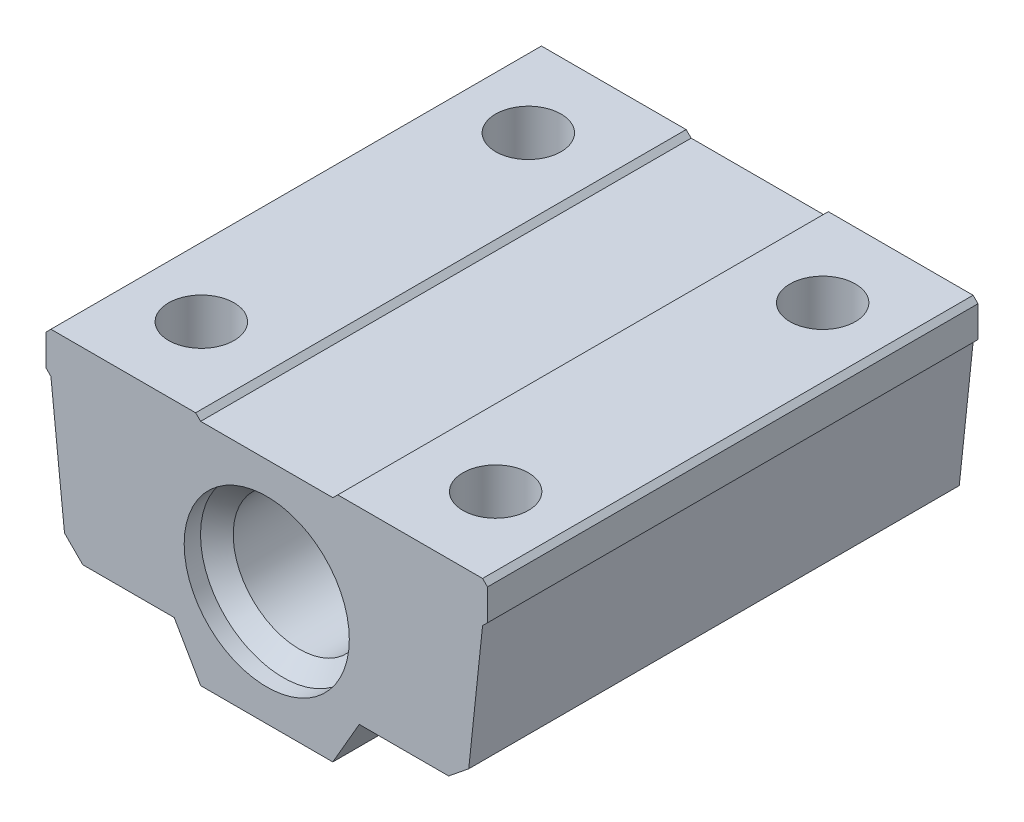
SolidWorks part; units mm, degrees
ref_plane "Front (XY)" through (0, 0, 0) normal (0, 0, 1) x (1, 0, 0)
ref_plane "Top (XZ)" through (0, 0, 0) normal (0, 1, 0) x (1, 0, 0)
ref_plane "Right (YZ)" through (0, 0, 0) normal (1, 0, 0) x (0, 0, -1)
sketch "Sketch1" plane through (0, 0, 0) normal (0, 0, 1) x (1, 0, 0)
  circle A0 centre (0, 0) radius 4.05
  dimension "D1" = 8.1
sketch "Sketch2" plane through (0, 0, 0) normal (0, 0, 1) x (1, 0, 0)
  line L1 (4.0415, -7) -> (8.0829, 0)
  line L2 (8.0829, 0) -> (4.0415, 7)
  line L3 (4.0415, 7) -> (-4.0415, 7)
  line L4 (-4.0415, 7) -> (-8.0829, 0)
  line L5 (-8.0829, 0) -> (-4.0415, -7)
  line L6 (-4.0415, -7) -> (4.0415, -7)
  circle A0 centre (0, 0) radius 7 construction
  dimension "D1" = 14
extrude "Boss-Extrude1" add sketch "Sketch2" along normal mid plane 30
sketch "Sketch3" plane through (0, 0, 0) normal (0, 0, 1) x (1, 0, 0)
  line L0 (0, 0) -> (0, 2.5047) construction
  circle A2 centre (0, 0) radius 5.05
  circle A3 centre (0, 0) radius 5.05
  dimension "D1" = 1
sketch "Sketch4" plane through (0, 0, 0) normal (0, 0, 1) x (1, 0, 0)
  line L0 (4.0415, -7) -> (8.0829, 0) construction
  line L1 (5.658, -4.2) -> (13.5, -4.2)
  line L2 (13.5, -4.2) -> (13.5, 7.3)
  line L3 (13.5, 7.3) -> (4.0452, 7.3)
  line L4 (4.0452, 7.3) -> (4.0415, 7)
  line L5 (0, 0) -> (0, -2.102) construction
  line L6 (4.0415, 7) -> (-4.0415, 7) construction
  line L7 (4.0415, 7) -> (-4.0415, 7)
  line L8 (-4.0452, 7.3) -> (-4.0415, 7)
  line L9 (-13.5, 7.3) -> (-4.0452, 7.3)
  line L10 (-13.5, -4.2) -> (-13.5, 7.3)
  line L11 (-5.658, -4.2) -> (-13.5, -4.2)
  line L12 (-4.0415, -7) -> (4.0415, -7) construction
  line L13 (-8.0829, 0) -> (-4.0415, -7) construction
  line L14 (4.0415, -7) -> (5.658, -4.2)
  line L15 (-4.0415, -7) -> (4.0415, -7)
  line L16 (-5.658, -4.2) -> (-4.0415, -7)
  dimension "D1" = 13.5
  dimension "D2" = 11.5
  dimension "D3" = 0.3
  dimension "D4" = 9.4548
extrude "Boss-Extrude2" add sketch "Sketch4" along normal mid plane 30
chamfer "Chamfer1" distance 0.3 angle 45 4 edges at (4.0452, 7.3, 0) (-4.0452, 7.3, 0) (13.5, 7.3, 0) (-13.5, 7.3, 0) first distance on face at (8.7726, 7.3, 0) first distance on face at (-4.0433, 7.15, 0) first distance on face at (13.5, 1.55, 0) first distance on face at (-13.5, 1.55, 0)
sketch "Sketch5" plane through (0, 0, 0) normal (0, 0, 1) x (1, 0, 0)
  line L0 (5.658, -4.2) -> (13.5, -4.2) construction
  line L1 (13.5, -4.2) -> (13.5, 7) construction
  line L2 (12.25, -4.2) -> (13.5, -4.2)
  line L3 (13.5, -4.2) -> (13.5, 4.8)
  line L4 (13.5, 4.8) -> (13.2, 4.8)
  line L5 (13.2, 4.8) -> (12.25, -4.2)
  line L6 (0, 0) -> (0, -1.632) construction
  line L7 (-13.2, 4.8) -> (-12.25, -4.2)
  line L8 (-13.5, 4.8) -> (-13.2, 4.8)
  line L9 (-13.5, -4.2) -> (-13.5, 4.8)
  line L10 (-12.25, -4.2) -> (-13.5, -4.2)
  dimension "D1" = 9
  dimension "D2" = 0.3
  dimension "D3" = 9.05
extrude "Cut-Extrude1" cut sketch "Sketch5" against normal through all both and the other way through all
chamfer "Chamfer2" distance 0.3 angle 45 2 edges at (-13.5, 4.8, 0) (13.5, 4.8, 0)
chamfer "Chamfer3" distance 1 angle 45 2 edges at (12.25, -4.2, 0) (-12.25, -4.2, 0) first distance on face at (12.725, 0.3, 0) first distance on face at (-8.954, -4.2, 0)
extrude "Cut-Extrude2" cut sketch "Sketch3" against normal through all both and the other way through all
sketch "Sketch6" plane through (0, 0, 0) normal (0, 0, 1) x (1, 0, 0)
  circle A2 centre (0, 0) radius 5.05 construction
  circle A3 centre (0, 0) radius 5.05
extrude "Boss-Extrude3" add sketch "Sketch6" along normal mid plane 28 separate body
sketch "Sketch7" plane through (0, 0, 0) normal (0, 0, 1) x (1, 0, 0)
  circle A0 centre (0, 0) radius 4.05 construction
  circle A1 centre (0, 0) radius 4.05
extrude "Cut-Extrude3" cut sketch "Sketch7" against normal through all both and the other way through all
chamfer "Chamfer4" distance 1 angle 45 2 edges at (4.05, 0, 14) (4.05, 0, -14)
sketch "Sketch8" plane through (0, 7.3, 0) normal (0, 1, 0) x (1, 0, 0)
  circle A0 centre (-9, 10) radius 2
  circle A1 centre (9, 10) radius 2
  circle A2 centre (9, -10) radius 2
  circle A3 centre (-9, -10) radius 2
  point P8 (0, 0)
  point P9 (0, 0)
  point P10 (0, 0)
  point P11 (0, 0)
  dimension "D1" = 9
  dimension "D5" = 4
  dimension "D2" = 9
  dimension "D3" = 20
  dimension "D4" = 10
extrude "Cut-Extrude4" cut sketch "Sketch8" against normal through all
